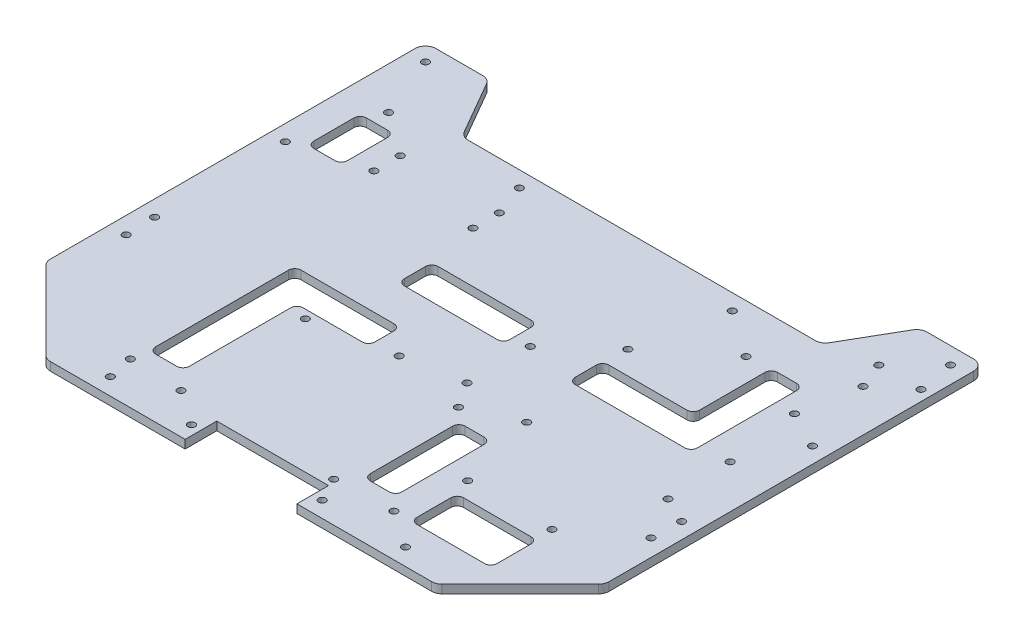
SolidWorks part; units mm, degrees
material "Acier non allié"
ref_plane "Front" through (0, 0, 0) normal (0, 0, 1) x (1, 0, 0)
ref_plane "Top" through (0, 0, 0) normal (0, 1, 0) x (1, 0, 0)
ref_plane "Right" through (0, 0, 0) normal (1, 0, 0) x (0, 0, -1)
sketch "Main scetch" plane through (0, 0, 0) normal (0, 1, 0) x (1, 0, 0)
  line L1 (0, 0) -> (132.5, 0) construction
  line L2 (0, 0) -> (0, 220) construction
  line L3 (0, 220) -> (132.5, 220) construction
  line L4 (132.5, 0) -> (132.5, 220) construction
  line L13 (-92.5, 0) -> (92.5, 0)
  line L14 (92.5, 0) -> (132.5, 40)
  line L15 (132.5, 40) -> (132.5, 220)
  line L16 (132.5, 220) -> (102.5, 220)
  line L17 (102.5, 220) -> (85.1795, 190)
  line L18 (85.1795, 190) -> (-85.1795, 190)
  line L19 (-102.5, 220) -> (-85.1795, 190)
  line L20 (-132.5, 220) -> (-102.5, 220)
  line L21 (-132.5, 40) -> (-132.5, 220)
  line L22 (-92.5, 0) -> (-132.5, 40)
  point P11 (0, 190)
  dimension "132.5" = 132.5
  dimension "D2" = 220
  dimension "D1" = 40
  dimension "D3" = 40
  dimension "D4" = 30
  dimension "D5" = 60
  dimension "D6" = 30
extrude "Main extrusion" add sketch "Main scetch" along normal blind 4
fillet "Congé1" radius 5 10 edges at (-132.5, 2, -40) (-92.5, 2, 0) (92.5, 2, 0) (132.5, 2, -40) (132.5, 2, -220) (102.5, 2, -220) (85.1795, 2, -190) (-85.1795, 2, -190) (-102.5, 2, -220) (-132.5, 2, -220)
sketch "Esquisse1" plane through (0, 4, 0) normal (0, 1, 0) x (1, 0, 0)
  line L0 (0, 0) -> (0, 218.5516) construction
  line L1 (132.5, 42.0711) -> (132.5, 215) construction
  line L2 (127.5, 220) -> (105.3868, 220) construction
  line L3 (-90.4289, 0) -> (90.4289, 0) construction
  circle A0 centre (70, 8) radius 1
  circle A1 centre (124.5, 70) radius 1
  circle A2 centre (124.5, 212) radius 1
  circle A3 centre (-124.5, 212) radius 1
  circle A4 centre (-124.5, 70) radius 1
  circle A5 centre (-70, 8) radius 1
  dimension "D1" = 2
  dimension "D2" = 2
  dimension "D3" = 2
  dimension "D4" = 8
  dimension "D5" = 8
  dimension "D6" = 8
  dimension "D7" = 8
  dimension "D8" = 70
  dimension "D9" = 70
extrude "Enlèv. mat.-Extru.1" cut sketch "Esquisse1" against normal through all
hole_wizard "Dégagement M31" positions "Esquisse2" profile "Esquisse3" hole size "M3" standard "ISO" end condition through all
sketch "Esquisse2" plane through (0, 4, 0) normal (0, 1, 0) x (1, 0, 0)
  point P0 (-124.5, 212)
  point P3 (-124.5, 70)
  point P6 (-70, 8)
  point P9 (70, 8)
  point P12 (124.5, 70)
  point P15 (124.5, 212)
sketch "Esquisse3" plane through (-124.5, 4, -212) normal (1, 0, 0) x (0, 0, 1)
  line L0 (0, 0) -> (0, 4)
  line L1 (0, 4) -> (1.7, 4)
  line L2 (1.7, 4) -> (1.7, 0)
  line L5 (1.7, 0) -> (0, 0)
  line L11 (0, -6.35) -> (0, 107.95) construction
  dimension "Diamètre du perçage jusqu'au prochain" = 3.4
  dimension "Profondeur du perçage jusqu'au prochain" = 4
sketch "Esquisse4" plane through (0, 4, 0) normal (0, 1, 0) x (1, 0, 0)
  line L0 (-132.5, 215) -> (-132.5, 42.0711) construction
  line L1 (-125, 146) -> (-125, 84) construction
  line L2 (82.2927, 190) -> (-82.2927, 190) construction
  line L3 (132.5, 42.0711) -> (132.5, 215) construction
  line L4 (-90.4289, 0) -> (90.4289, 0) construction
  line L5 (127.5, 220) -> (105.3868, 220) construction
  line L8 (-105.3868, 220) -> (-127.5, 220) construction
  line L9 (-31, 7.5) -> (31, 7.5) construction
  line L10 (125, 146) -> (125, 84) construction
  line L11 (-26.5, 0) -> (26.5, 0)
  line L12 (-26.5, 0) -> (-26.5, 15)
  line L13 (-26.5, 15) -> (26.5, 15)
  line L14 (26.5, 0) -> (26.5, 15)
  line L15 (50.5, 182.5) -> (112.5, 182.5) construction
  line L16 (-112.5, 182.5) -> (-50.5, 182.5) construction
  circle A1 centre (-68.5, 185) radius 1 construction
  circle A5 centre (72.5, 167) radius 1
  circle A6 centre (41.5, 142) radius 1
  circle A7 centre (107.5, 155) radius 1
  circle A8 centre (127.5, 195) radius 1
  circle A9 centre (112, 120) radius 1
  circle A10 centre (112.5, 90) radius 1
  circle A11 centre (17.2, 120) radius 1
  circle A12 centre (17.2, 90) radius 1
  circle A13 centre (47.5, 88) radius 1
  circle A14 centre (57.5, 50) radius 1
  circle A15 centre (97.5, 50) radius 1
  circle A16 centre (52.5, 20) radius 1
  circle A17 centre (-10, 85) radius 1
  circle A18 centre (-72.5, 20) radius 1
  circle A19 centre (107.5, 195) radius 1
  circle A23 centre (-47.5, 78) radius 1
  circle A24 centre (25.14, 78) radius 1
  circle A25 centre (-47.5, 19.07) radius 1
  circle A26 centre (25.1096, 18.82) radius 1
  circle A27 centre (-92, 167.5) radius 1
  circle A28 centre (-45, 167.5) radius 1
  circle A29 centre (-92, 155) radius 1
  circle A30 centre (-45, 155) radius 1
  circle A31 centre (-125, 146) radius 1
  circle A32 centre (-125, 84) radius 1
  circle A33 centre (-31, 7.5) radius 1
  circle A34 centre (31, 7.5) radius 1
  circle A35 centre (125, 146) radius 1
  circle A36 centre (125, 84) radius 1
  circle A37 centre (50.5, 182.5) radius 1
  circle A38 centre (112.5, 182.5) radius 1
  circle A39 centre (-112.5, 182.5) radius 1
  circle A40 centre (-50.5, 182.5) radius 1
  point P63 (-125, 115)
  point P69 (0, 7.5)
  point P74 (0, 15)
  point P79 (125, 115)
  dimension "D4" = 2
  dimension "D13" = 2
  dimension "D16" = 2
  dimension "D19" = 2
  dimension "D24" = 2
  dimension "D25" = 2
  dimension "D28" = 2
  dimension "D30" = 2
  dimension "D32" = 2
  dimension "D36" = 2
  dimension "D37" = 2
  dimension "D40" = 2
  dimension "D48" = 2
  dimension "D49" = 2
  dimension "D50" = 2
  dimension "D52" = 2
  dimension "D11" = 2
  dimension "D12" = 2
  dimension "D65" = 2
  dimension "D66" = 2
  dimension "D58" = 2
  dimension "D61" = 2
  dimension "D70" = 2
  dimension "D71" = 2
  dimension "D72" = 2
  dimension "D73" = 2
  dimension "D77" = 2
  dimension "D78" = 2
  dimension "D85" = 2
  dimension "D86" = 2
  dimension "D89" = 2
  dimension "D90" = 2
  dimension "D94" = 2
  dimension "D95" = 2
  dimension "D14" = 205
  dimension "D15" = 23
  dimension "D20" = 25
  dimension "D21" = 65
  dimension "D22" = 5
  dimension "D23" = 25
  dimension "D26" = 20.5
  dimension "D27" = 100
  dimension "D29" = 30
  dimension "D31" = 115.3
  dimension "D33" = 115.3
  dimension "D34" = 132
  dimension "D35" = 85
  dimension "D38" = 50
  dimension "D39" = 75
  dimension "D41" = 35
  dimension "D42" = 80
  dimension "D43" = 20
  dimension "D44" = 20
  dimension "D45" = 205
  dimension "D46" = 85
  dimension "D47" = 142.5
  dimension "D51" = 25
  dimension "D53" = 25
  dimension "D54" = 5
  dimension "D55" = 64
  dimension "D7" = 59.18
  dimension "D8" = 72.64
  dimension "D9" = 58.93
  dimension "D10" = 72.61
  dimension "D67" = 85
  dimension "D68" = 78
  dimension "D56" = 23.5
  dimension "D57" = 23.5
  dimension "D59" = 17.5
  dimension "D60" = 17.5
  dimension "D62" = 12.5
  dimension "D63" = 12.5
  dimension "D64" = 23.5
  dimension "D69" = 23.5
  dimension "D17" = 25
  dimension "D18" = 31
  dimension "D76" = 62
  dimension "D74" = 7.5
  dimension "D75" = 105
  dimension "D79" = 7.5
  dimension "D80" = 132.5
  dimension "D81" = 62
  dimension "D82" = 15
  dimension "D83" = 53
  dimension "D84" = 62
  dimension "D87" = 7.5
  dimension "D88" = 105
  dimension "D91" = 62
  dimension "D92" = 7.5
  dimension "D96" = 62
  dimension "D97" = 7.5
  dimension "D98" = 20
  dimension "D93" = 20
extrude "Enlèv. mat.-Extru.2" cut sketch "Esquisse4" against normal through all
hole_wizard "Dégagement M32" positions "Esquisse5" profile "Esquisse6" hole size "M3" standard "ISO" end condition through all
sketch "Esquisse5" plane through (0, 4, 0) normal (0, 1, 0) x (1, 0, 0)
  point P9 (17.2, 120)
  point P18 (41.5, 142)
  point P21 (72.5, 167)
  point P24 (107.5, 155)
  point P27 (127.5, 195)
  point P30 (112, 120)
  point P33 (112.5, 90)
  point P36 (47.5, 88)
  point P39 (17.2, 90)
  point P42 (57.5, 50)
  point P45 (97.5, 50)
  point P48 (-10, 85)
  point P51 (-72.5, 20)
  point P54 (52.5, 20)
  point P57 (107.5, 195)
  point P86 (-47.5, 78)
  point P89 (25.14, 78)
  point P92 (-47.5, 19.07)
  point P95 (25.1096, 18.82)
  point P102 (-92, 167.5)
  point P105 (-92, 155)
  point P108 (-45, 155)
  point P111 (-45, 167.5)
  point P114 (-125, 146)
  point P117 (-125, 84)
  point P121 (-31, 7.5)
  point P124 (31, 7.5)
  point P128 (125, 146)
  point P131 (125, 84)
  point P134 (-112.5, 182.5)
  point P137 (-50.5, 182.5)
  point P140 (50.5, 182.5)
  point P143 (112.5, 182.5)
sketch "Esquisse6" plane through (17.2, 4, -120) normal (1, 0, 0) x (0, 0, 1)
  line L0 (0, 0) -> (0, 4)
  line L1 (0, 4) -> (1.7, 4)
  line L2 (1.7, 4) -> (1.7, 0)
  line L5 (1.7, 0) -> (0, 0)
  line L11 (0, -6.35) -> (0, 107.95) construction
  dimension "Diamètre du perçage jusqu'au prochain" = 3.4
  dimension "Profondeur du perçage jusqu'au prochain" = 4
sketch "Esquisse7" plane through (0, 4, 0) normal (0, 1, 0) x (1, 0, 0)
  line L0 (-90.4289, 0) -> (-26.5, 0) construction
  line L1 (-40.5, 131) -> (9.5, 131)
  line L2 (-40.5, 131) -> (-40.5, 115)
  line L3 (-40.5, 115) -> (9.5, 115)
  line L4 (9.5, 131) -> (9.5, 115)
  line L5 (-132.5, 215) -> (-132.5, 42.0711) construction
  line L8 (40.5, 115) -> (98.5, 115)
  line L10 (132.5, 42.0711) -> (132.5, 215) construction
  line L11 (40.5, 115) -> (40.5, 131)
  line L12 (83.5, 168) -> (98.5, 168)
  line L13 (83.5, 168) -> (83.5, 131)
  line L15 (98.5, 168) -> (98.5, 115)
  line L16 (40.5, 131) -> (83.5, 131)
  line L17 (-105.3868, 220) -> (-127.5, 220) construction
  line L18 (60.5, 42) -> (98.5, 42)
  line L19 (60.5, 42) -> (60.5, 20)
  line L20 (60.5, 20) -> (98.5, 20)
  line L21 (98.5, 42) -> (98.5, 20)
  line L22 (-118.5, 175) -> (-102.5, 175)
  line L23 (-118.5, 175) -> (-118.5, 150)
  line L24 (-118.5, 150) -> (-102.5, 150)
  line L25 (-102.5, 175) -> (-102.5, 150)
  line L27 (-71.5, 28) -> (-55.5, 28)
  line L28 (-71.5, 28) -> (-71.5, 83)
  line L30 (-55.5, 28) -> (-55.5, 82)
  line L31 (31.5, 71.82) -> (46.5, 71.82)
  line L32 (31.5, 71.82) -> (31.5, 26.82)
  line L33 (31.5, 26.82) -> (46.5, 26.82)
  line L34 (46.5, 71.82) -> (46.5, 26.82)
  line L35 (-71.5, 97) -> (-21.5, 97)
  line L36 (-71.5, 97) -> (-71.5, 83)
  line L37 (-55.5, 82) -> (-21.5, 82)
  line L38 (-21.5, 97) -> (-21.5, 82)
  circle A0 centre (-72.5, 20) radius 1.7 construction
  circle A1 centre (-47.5, 78) radius 1.7 construction
  circle A2 centre (25.1096, 18.82) radius 1.7 construction
  circle A3 centre (52.5, 20) radius 1.7 construction
  dimension "D19" = 8
  dimension "D20" = 8
  dimension "D24" = 15
  dimension "D1" = 50
  dimension "D2" = 16
  dimension "D3" = 131
  dimension "D4" = 92
  dimension "D5" = 16
  dimension "D6" = 53
  dimension "D7" = 43
  dimension "D8" = 115
  dimension "D9" = 72
  dimension "D10" = 38
  dimension "D11" = 34
  dimension "D12" = 15
  dimension "D13" = 22
  dimension "D14" = 20
  dimension "D15" = 30
  dimension "D16" = 70
  dimension "D17" = 16
  dimension "D18" = 25
  dimension "D21" = 16
  dimension "D22" = 55
  dimension "D23" = 8
  dimension "6" = 6
  dimension "D25" = 45
  dimension "D26" = 50
  dimension "D27" = 54
  dimension "D28" = 15
extrude "Enlèv. mat.-Extru.3" cut sketch "Esquisse7" against normal up to surface (4 mm away) up to face at (17.2, 0, -118.3)
fillet "Congé2" radius 3 28 edges at (60.5, 2, -42) (60.5, 2, -20) (98.5, 2, -20) (98.5, 2, -42) (98.5, 2, -168) (98.5, 2, -115) (83.5, 2, -168) (40.5, 2, -131) (83.5, 2, -131) (40.5, 2, -115) (-40.5, 2, -115) (9.5, 2, -115) (9.5, 2, -131) (-40.5, 2, -131) (-118.5, 2, -150) (-102.5, 2, -150) (-102.5, 2, -175) (-118.5, 2, -175) (-55.5, 2, -28) (-71.5, 2, -28) (46.5, 2, -26.82) (31.5, 2, -26.82) (46.5, 2, -71.82) (31.5, 2, -71.82) (-21.5, 2, -82) (-21.5, 2, -97) (-55.5, 2, -82) (-71.5, 2, -97)
equation "\"WIDTH\"= 300mm'Total width of the robot"
equation "\"LENGTH\"= 220mm'Total length of the robot"
equation "\"D2@Main scetch\" = \"LENGTH\""
equation "\"CUT_DEPTH\"= 45mm'Depth of the cut on the edges of the plate"
equation "\"Plate_th\"= 3mm'Thickness of the plate"
equation "\"D1\"= \"Plate_th\""
equation "\"D47@Esquisse4\"=(80+205)/2"
